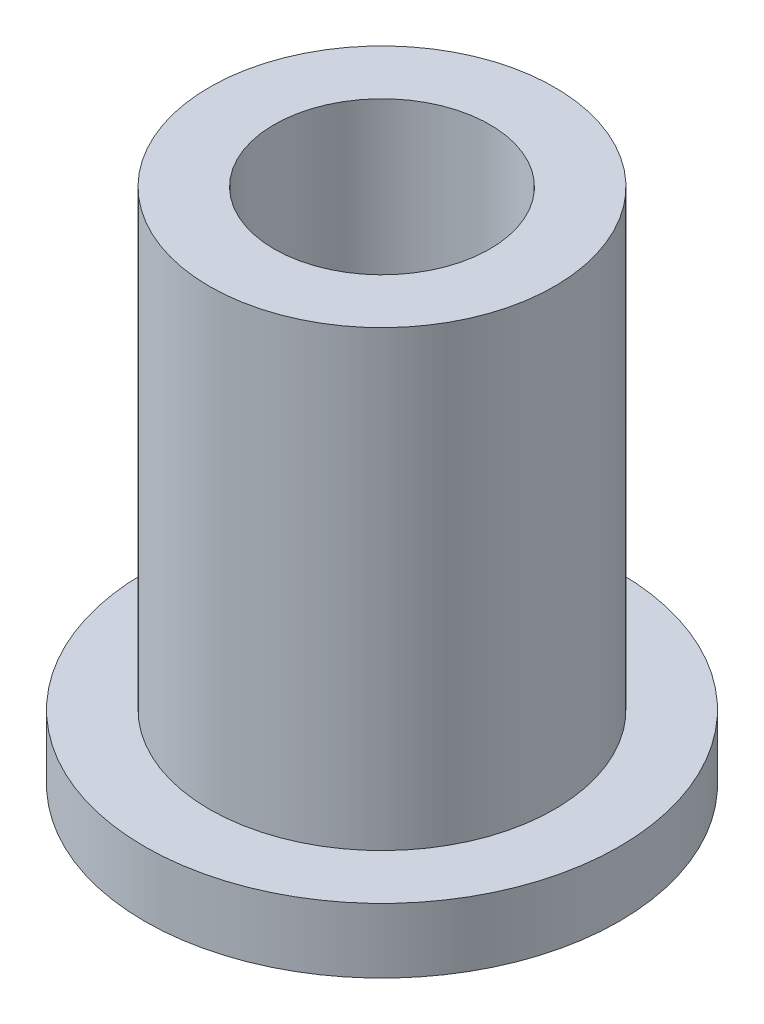
SolidWorks part; units mm, degrees
ref_plane "Front" through (0, 0, 0) normal (0, 0, 1) x (1, 0, 0)
ref_plane "Top" through (0, 0, 0) normal (0, 1, 0) x (1, 0, 0)
ref_plane "Right" through (0, 0, 0) normal (1, 0, 0) x (0, 0, -1)
sketch "Sketch1" plane through (0, 0, 0) normal (0, 1, 0) x (1, 0, 0)
  circle A0 centre (0, 0) radius 2.5
  circle A1 centre (0, 0) radius 4
  circle A2 centre (0, 0) radius 5.5
  dimension "ID" = 5
  dimension "OD" = 8
  dimension "FlangeOD" = 11
sketch "Sketch2" plane through (0, 0, 0) normal (0, 1, 0) x (1, 0, 0)
  circle A0 centre (0, 0) radius 2.5 construction
  circle A1 centre (0, 0) radius 4 construction
  circle A2 centre (0, 0) radius 2.5
  circle A3 centre (0, 0) radius 4
extrude "Boss-Extrude1" add sketch "Sketch2" along normal blind 12
sketch "Sketch3" plane through (0, 0, 0) normal (0, 1, 0) x (1, 0, 0)
  circle A0 centre (0, 0) radius 5.5 construction
  circle A1 centre (0, 0) radius 4 construction
  circle A2 centre (0, 0) radius 5.5
  circle A3 centre (0, 0) radius 4
extrude "Boss-Extrude2" add sketch "Sketch3" along normal blind 1.5
ref_plane "Contact Plane 1" through (0, 14.54, 0) normal (0, 1, 0) x (1, 0, 0)
ref_plane "Contact Plane 2" through (0, 0, 0) normal (0, -1, 0) x (-1, 0, 0)
ref_axis "Center Axis 1" through (0, 12, 0) along (0, -1, 0)
